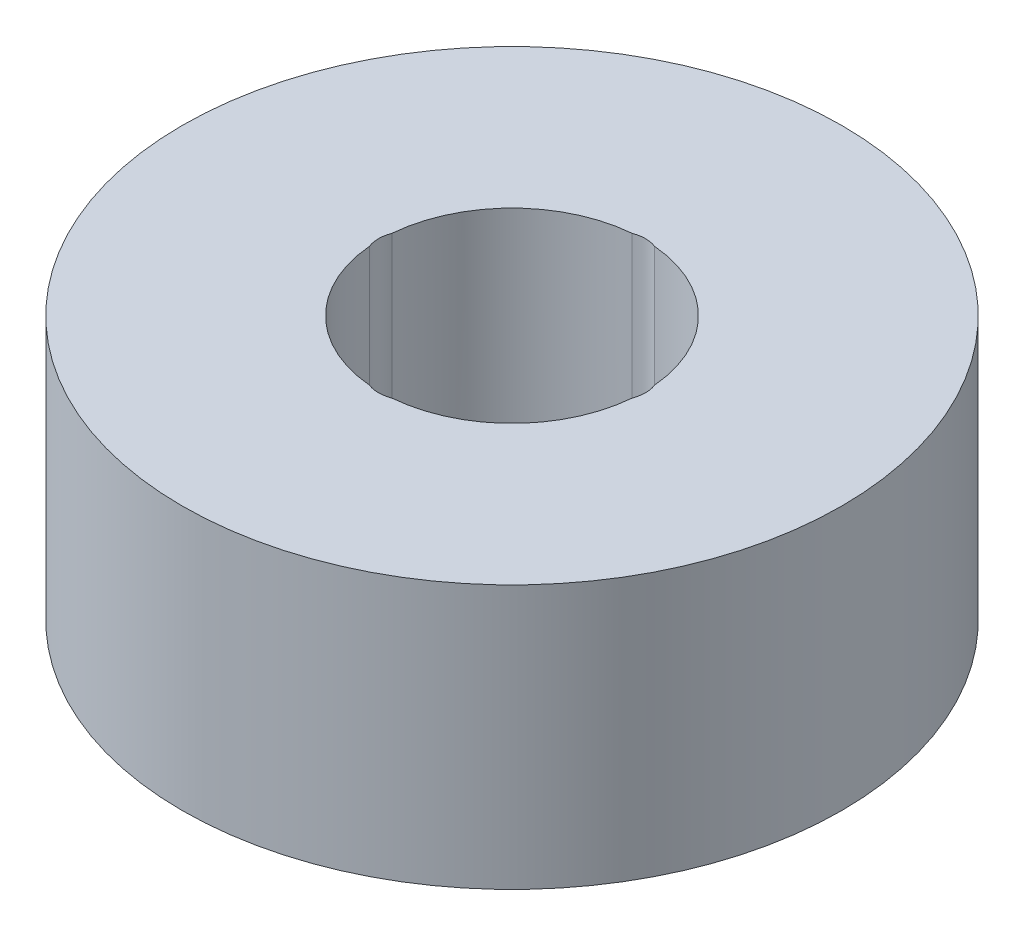
SolidWorks part; units mm, degrees
ref_plane "Front Plane" through (0, 0, 0) normal (0, 0, 1) x (1, 0, 0)
ref_plane "Top Plane" through (0, 0, 0) normal (0, 1, 0) x (1, 0, 0)
ref_plane "Right Plane" through (0, 0, 0) normal (1, 0, 0) x (0, 0, -1)
sketch "Sketch1" plane through (0, 0, 0) normal (0, 1, 0) x (1, 0, 0)
  circle A0 centre (0, 0) radius 25
  dimension "FLANGE_OD" = 50
extrude "Boss-Extrude1" add sketch "Sketch1" along normal blind 20
sketch "Sketch2" plane through (0, 0, 0) normal (0, 1, 0) x (1, 0, 0)
  circle A0 centre (0, 0) radius 10
  dimension "BORE_D" = 20
extrude "Cut-Extrude1" cut sketch "Sketch2" along normal through all
sketch "Sketch3" plane through (0, 20, 0) normal (0, 1, 0) x (1, 0, 0)
  circle A0 centre (0, 0) radius 7.7639 construction
  circle A1 centre (-7.7639, 0) radius 2.3596
  dimension "BOLT_D" = 4.7192
  dimension "BOLT_PCD" = 15.5278
extrude "Cut-Extrude2" cut sketch "Sketch3" against normal blind 13.5477
pattern_circular "CirPattern1" count 4 over 360 about axis through (0, 0, 0) along (0, 1, 0) of "Cut-Extrude2"
